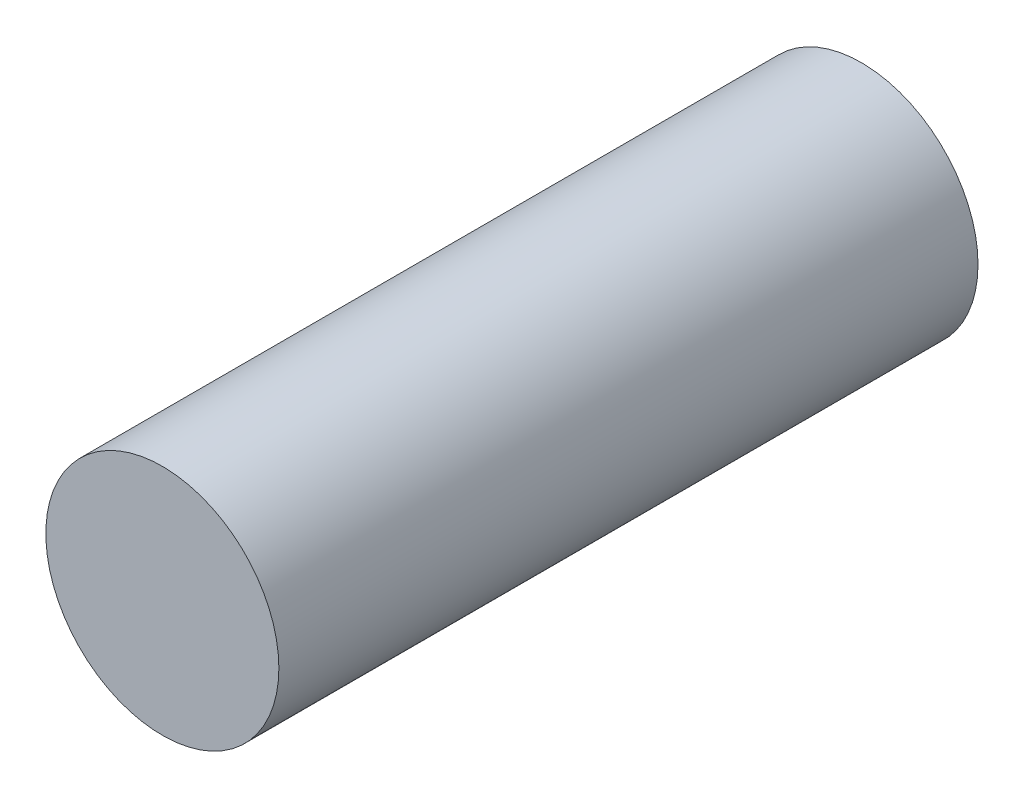
SolidWorks part; units mm, degrees
ref_plane "Front Plane" through (0, 0, 0) normal (0, 0, 1) x (1, 0, 0)
ref_plane "Top Plane" through (0, 0, 0) normal (0, 1, 0) x (1, 0, 0)
ref_plane "Right Plane" through (0, 0, 0) normal (1, 0, 0) x (0, 0, -1)
sketch "Sketch1" plane through (0, 0, 0) normal (0, 0, 1) x (1, 0, 0)
  circle A0 centre (0, 0) radius 5
  dimension "D1" = 10
extrude "Boss-Extrude1" add sketch "Sketch1" along normal blind 30
sketch "Sketch2" plane through (0, 0, 0) normal (0, 0, -1) x (-1, 0, 0)
  line L6 (-0.5, -1.4142) -> (-0.5, -2.514)
  line L7 (-0.5, -2.514) -> (0.5, -2.514)
  line L8 (0.5, -1.4142) -> (0.5, -2.514)
  arc A1 (0.5, -1.4142) -> (-0.5, -1.4142) centre (0, 0) ccw
  point P3 (0, -1.5)
  dimension "D1" = 3
  dimension "D3" = 1
extrude "Cut-Extrude1" cut sketch "Sketch2" against normal blind 20
